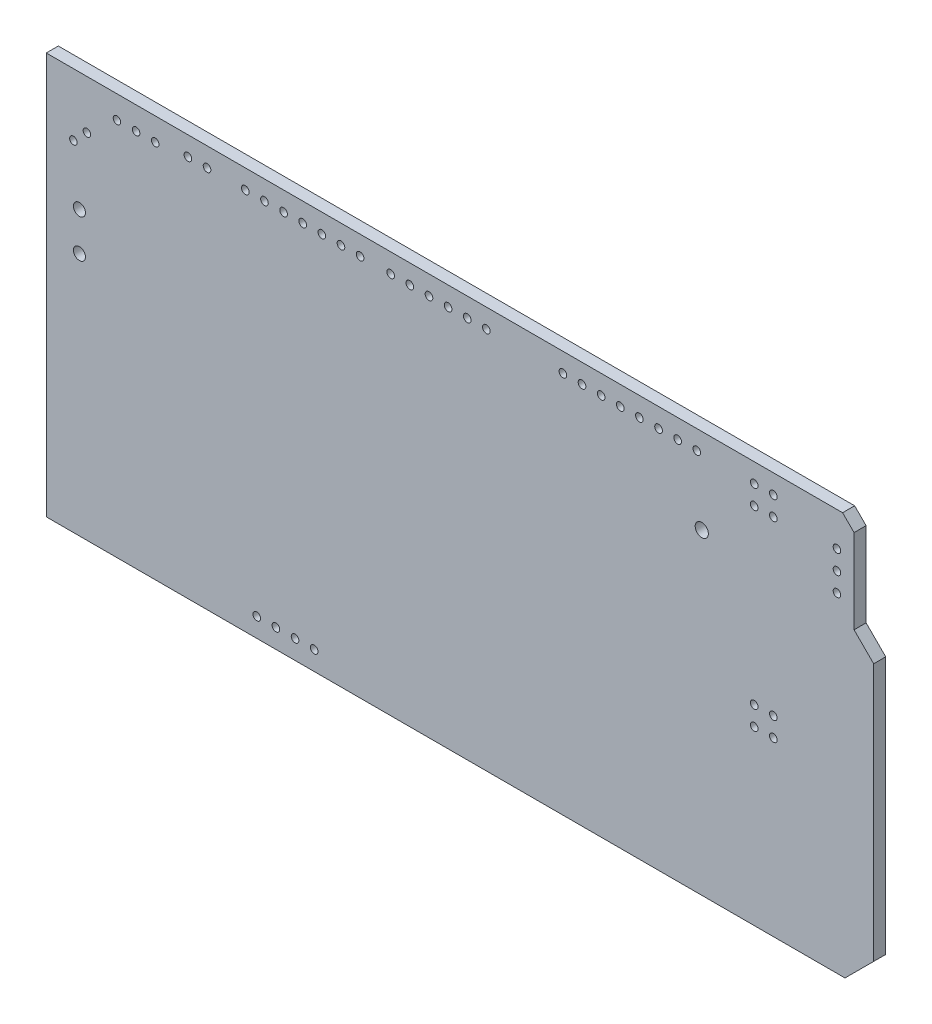
SolidWorks part; units mm, degrees
ref_plane "Front Plane" through (0, 0, 0) normal (0, 0, 1) x (1, 0, 0)
ref_plane "Top Plane" through (0, 0, 0) normal (0, 1, 0) x (1, 0, 0)
ref_plane "Right Plane" through (0, 0, 0) normal (1, 0, 0) x (0, 0, -1)
sketch "Sketch1" plane through (0, 0, 0) normal (0, 0, 1) x (1, 0, 0)
  line L0 (110.1725, -141.9225) -> (216.2175, -141.9225)
  line L1 (216.2175, -141.9225) -> (220.0275, -138.1125)
  line L2 (220.0275, -138.1125) -> (220.0275, -103.886)
  line L3 (220.0275, -103.886) -> (217.424, -101.2825)
  line L4 (217.424, -101.2825) -> (217.424, -90.17)
  line L5 (217.424, -90.17) -> (217.424, -90.1065)
  line L6 (217.424, -90.1065) -> (215.9, -88.5825)
  line L7 (215.9, -88.5825) -> (110.1725, -88.5825)
  line L8 (110.1725, -88.5825) -> (110.1725, -141.9225)
extrude "BOARD" add sketch "Sketch1" along normal blind 1.6 separate body
sketch "Sketch2" plane through (0, 0, 0) normal (0, 0, 1) x (1, 0, 0)
  circle A0 centre (139.4956, -99.9152) radius 0.8765
  circle A1 centre (139.4956, -99.9152) radius 0.8765
  circle A2 centre (197.2044, -99.9152) radius 0.8765
  circle A3 centre (197.2044, -99.9152) radius 0.8765
  circle A4 centre (114.575, -109.45) radius 0.8
  circle A5 centre (114.575, -104.37) radius 0.8
  circle A6 centre (124.64, -91.62) radius 0.5
  circle A7 centre (122.1, -91.62) radius 0.5
  circle A8 centre (119.56, -91.62) radius 0.5
  circle A9 centre (115.57, -95.0468) radius 0.5
  circle A10 centre (113.7739, -96.8428) radius 0.5
  circle A11 centre (215.15, -98.19) radius 0.5
  circle A12 centre (215.15, -95.65) radius 0.5
  circle A13 centre (215.15, -93.11) radius 0.5
  circle A14 centre (145.743, -139.385) radius 0.508
  circle A15 centre (143.203, -139.385) radius 0.508
  circle A16 centre (140.663, -139.385) radius 0.508
  circle A17 centre (196.543, -91.125) radius 0.508
  circle A18 centre (194.003, -91.125) radius 0.508
  circle A19 centre (191.463, -91.125) radius 0.508
  circle A20 centre (188.923, -91.125) radius 0.508
  circle A21 centre (186.383, -91.125) radius 0.508
  circle A22 centre (183.843, -91.125) radius 0.508
  circle A23 centre (181.303, -91.125) radius 0.508
  circle A24 centre (178.763, -91.125) radius 0.508
  circle A25 centre (168.603, -91.125) radius 0.508
  circle A26 centre (166.063, -91.125) radius 0.508
  circle A27 centre (163.523, -91.125) radius 0.508
  circle A28 centre (160.983, -91.125) radius 0.508
  circle A29 centre (158.443, -91.125) radius 0.508
  circle A30 centre (155.903, -91.125) radius 0.508
  circle A31 centre (136.599, -91.125) radius 0.508
  circle A32 centre (151.839, -91.125) radius 0.508
  circle A33 centre (149.299, -91.125) radius 0.508
  circle A34 centre (146.759, -91.125) radius 0.508
  circle A35 centre (128.979, -91.125) radius 0.508
  circle A36 centre (131.519, -91.125) radius 0.508
  circle A37 centre (139.139, -91.125) radius 0.508
  circle A38 centre (141.679, -91.125) radius 0.508
  circle A39 centre (144.219, -91.125) radius 0.508
  circle A40 centre (138.123, -139.385) radius 0.508
  circle A41 centre (204.163, -91.125) radius 0.508
  circle A42 centre (206.703, -91.125) radius 0.508
  circle A43 centre (204.163, -93.665) radius 0.508
  circle A44 centre (206.703, -93.665) radius 0.508
  circle A45 centre (204.163, -96.205) radius 0.508
  circle A46 centre (206.703, -96.205) radius 0.508
  circle A47 centre (204.163, -98.745) radius 0.508
  circle A48 centre (206.703, -98.745) radius 0.508
  circle A49 centre (204.163, -101.285) radius 0.508
  circle A50 centre (206.703, -101.285) radius 0.508
  circle A51 centre (204.163, -103.825) radius 0.508
  circle A52 centre (206.703, -103.825) radius 0.508
  circle A53 centre (204.163, -106.365) radius 0.508
  circle A54 centre (206.703, -106.365) radius 0.508
  circle A55 centre (204.163, -108.905) radius 0.508
  circle A56 centre (206.703, -108.905) radius 0.508
  circle A57 centre (204.163, -111.445) radius 0.508
  circle A58 centre (206.703, -111.445) radius 0.508
  circle A59 centre (204.163, -113.985) radius 0.508
  circle A60 centre (206.703, -113.985) radius 0.508
  circle A61 centre (204.163, -116.525) radius 0.508
  circle A62 centre (206.703, -116.525) radius 0.508
  circle A63 centre (204.163, -119.065) radius 0.508
  circle A64 centre (206.703, -119.065) radius 0.508
  point P128 (0, 0)
  point P129 (0, 0)
  point P130 (0, 0)
  point P131 (0, 0)
  point P132 (0, 0)
  point P133 (0, 0)
  point P134 (0, 0)
  point P135 (0, 0)
  point P136 (0, 0)
  point P137 (0, 0)
  point P138 (0, 0)
  point P139 (0, 0)
  point P140 (0, 0)
  point P141 (0, 0)
ref_plane "Plane1" through (0, 0, 1.6) normal (0, 0, 1) x (1, 0, 0)
extrude "Cut-Extrude3" cut sketch "Sketch2" along normal through all contours A7 | A6 | A35 | A4 | A5 | A9 | A10 | A8 | A2 | A17 | A18 | A19 | A20 | A21 | A22 | A23 | A24 | A42 | A41 | A13 | A12 | A11 | A44 | A43 | A63 | A64 | A14 | A15 | A16 | A40 | A61 | A62 | A31 | A36 | A25 | A26 | A27 | A28 | A29 | A30 | A32 | A33 | A34 | A39 | A38 | A37 region at (124.64, -91.62, 0) region at (122.1, -91.62, 0) region at (128.979, -91.125, 0)
